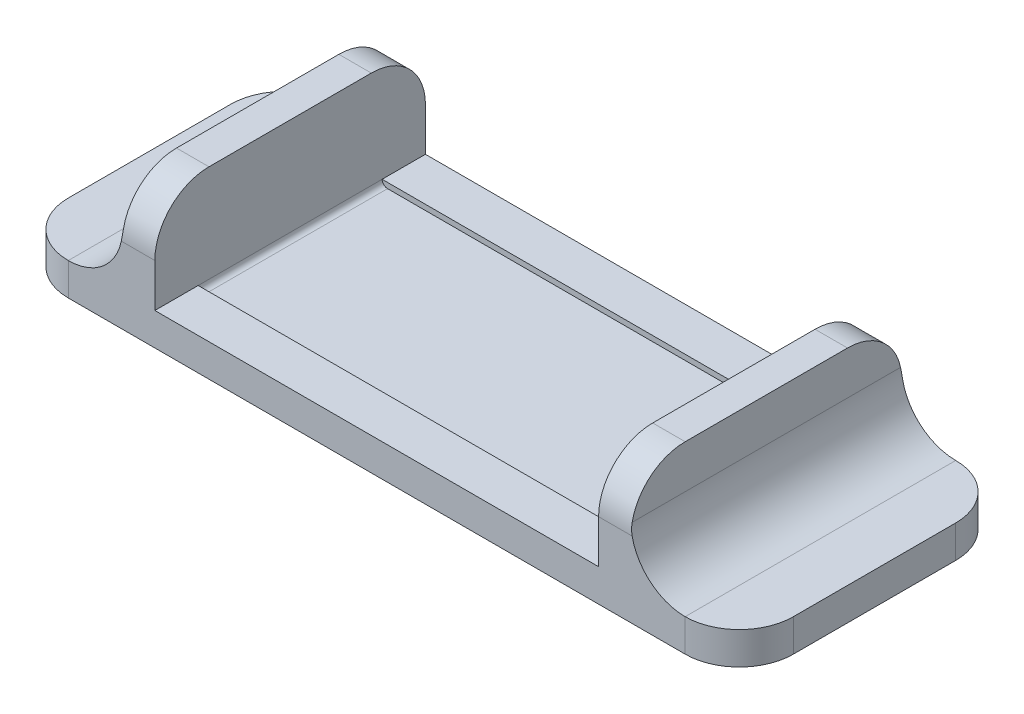
SolidWorks part; units mm, degrees
ref_plane "Front Plane" through (0, 0, 0) normal (0, 0, 1) x (1, 0, 0)
ref_plane "Top Plane" through (0, 0, 0) normal (0, 1, 0) x (1, 0, 0)
ref_plane "Right Plane" through (0, 0, 0) normal (1, 0, 0) x (0, 0, -1)
sketch "Sketch1" plane through (0, 0, 0) normal (0, 0, 1) x (1, 0, 0)
  line L0 (0, 0) -> (82, 0)
  line L1 (0, 0) -> (0, 18)
  line L2 (82, 0) -> (82, 18)
  line L3 (82, 18) -> (88, 18)
  line L4 (88, 18) -> (88, 0)
  line L5 (88, 0) -> (108, 0)
  line L6 (108, 0) -> (108, -6)
  line L7 (108, -6) -> (0, -6)
  line L8 (0, -6) -> (-6, -6)
  line L9 (-6, -6) -> (-26, -6)
  line L10 (-26, -6) -> (-26, 0)
  line L11 (-26, 0) -> (-6, 0)
  line L12 (-6, 0) -> (-6, 18)
  line L13 (-6, 18) -> (0, 18)
extrude "Boss-Extrude1" add sketch "Sketch1" along normal blind 50
fillet "Fillet1" radius 10 6 edges at (88, 0, 25) (-6, 0, 25) (108, -3, 0) (108, -3, 50) (-26, -3, 0) (-26, -3, 50)
fillet "Fillet2" radius 10 4 edges at (85, 18, 50) (85, 18, 0) (-3, 18, 0) (-3, 18, 50)
sketch "Sketch2" plane through (0, 0, 0) normal (0, 1, 0) x (1, 0, 0)
  line L4 (0, 0) -> (0, -8)
  line L5 (0, -50) -> (0, -42)
  line L6 (0, -50) -> (0, 0) construction
  line L7 (82, -40) -> (82, -50) construction
  line L8 (0, -8) -> (82, -8)
  line L9 (0, -8) -> (0, -42)
  line L10 (0, -42) -> (82, -42)
  line L11 (82, -8) -> (82, -42)
  line M2 (0, 0) -> (0, -50)
  line M4 (82, -50) -> (82, 0)
extrude "Cut-Extrude1" cut sketch "Sketch2" against normal blind 1 contours L10 L8 M2 M4 region at (41, 0, 25)
fillet "Fillet3" radius 1 2 edges at (82, -1, 25) (0, -1, 25)
